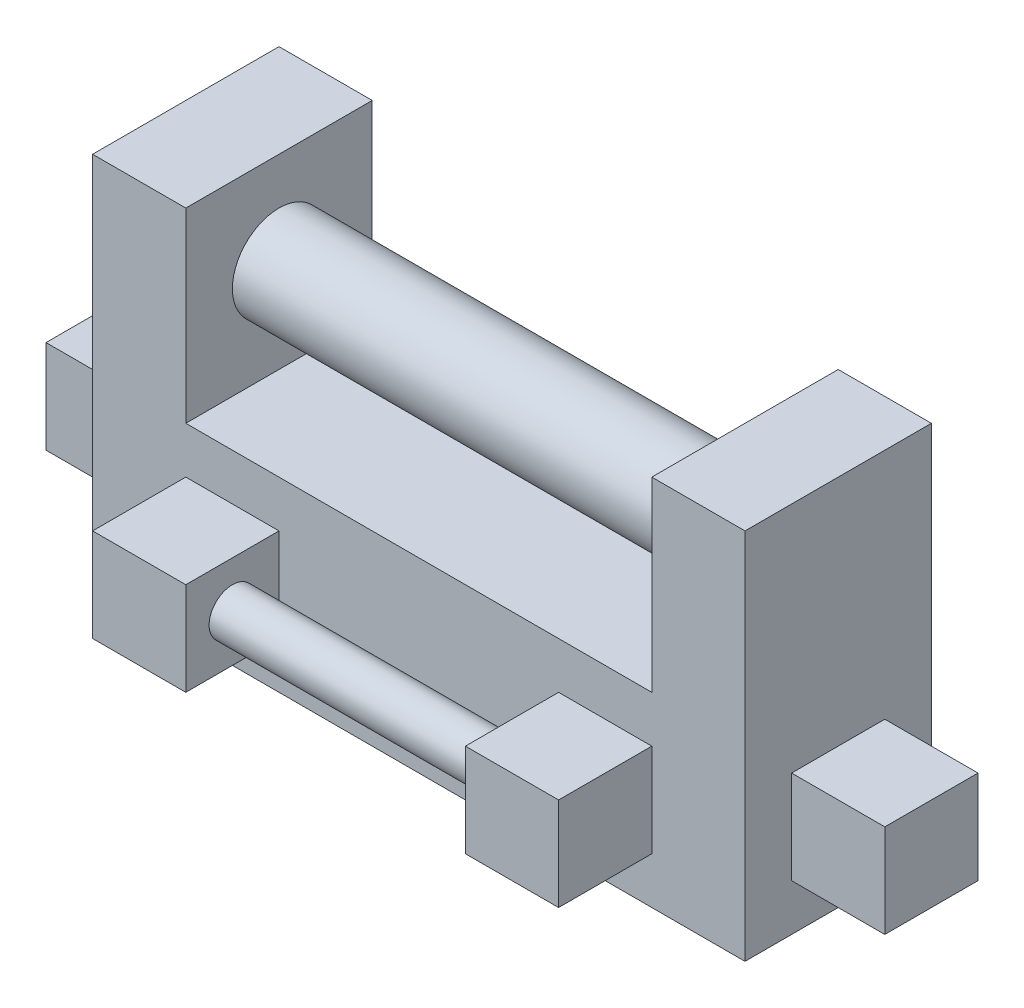
SolidWorks part; units mm, degrees
ref_plane "Front Plane" through (0, 0, 0) normal (0, 0, 1) x (1, 0, 0)
ref_plane "Top Plane" through (0, 0, 0) normal (0, 1, 0) x (1, 0, 0)
ref_plane "Right Plane" through (0, 0, 0) normal (1, 0, 0) x (0, 0, -1)
sketch "Sketch1" plane through (0, 0, 0) normal (0, 0, 1) x (1, 0, 0)
  line L0 (0, 0) -> (0, 40)
  line L1 (0, 40) -> (10, 40)
  line L2 (10, 40) -> (10, 20)
  line L3 (10, 20) -> (60, 20)
  line L4 (60, 20) -> (60, 40)
  line L5 (60, 40) -> (70, 40)
  line L6 (70, 40) -> (70, 0)
  line L7 (70, 0) -> (0, 0)
  line L9 (0, 5) -> (-10, 5)
  line L10 (0, 5) -> (0, 15)
  line L11 (0, 15) -> (-10, 15)
  line L12 (-10, 5) -> (-10, 15)
  line L13 (70, 5) -> (80, 5)
  line L14 (70, 5) -> (70, 15)
  line L15 (70, 15) -> (80, 15)
  line L16 (80, 5) -> (80, 15)
  line L17 (10, 5) -> (20, 5)
  line L18 (10, 5) -> (10, 15)
  line L19 (10, 15) -> (20, 15)
  line L20 (20, 5) -> (20, 15)
  line L21 (50, 5) -> (60, 5)
  line L22 (50, 5) -> (50, 15)
  line L23 (50, 15) -> (60, 15)
  line L24 (60, 5) -> (60, 15)
  point P25 (15, 5)
  dimension "D1" = 40
  dimension "D2" = 70
  dimension "D3" = 10
  dimension "D4" = 10
  dimension "D5" = 90
  dimension "D6" = 10
  dimension "D7" = 50
  dimension "D8" = 10
  dimension "D9" = 10
  dimension "D10" = 10
  dimension "D11" = 10
  dimension "D12" = 25
  dimension "D13" = 5
  dimension "D14" = 25
  dimension "D15" = 5
  dimension "D16" = 5
  dimension "D17" = 10
  dimension "D18" = 10
  dimension "D19" = 10
extrude "Boss-Extrude1" add sketch "Sketch1" along normal mid plane 20 contours L7 L6 L5 L4 L3 L2 L1 L0 L24 L21 L22 L23 L20 L17 L18 L19 region at (35, 15, 0)
extrude "Boss-Extrude2" add sketch "Sketch1<3>" along normal mid plane 10 contours L13 L16 L15 L6 | L12 L9 L0 L11 region at (-5, 10, 0) region at (75, 10, 0)
sketch "Sketch1<3>" plane through (0, 0, 0) normal (0, 0, 1) x (1, 0, 0) same geometry as "Sketch1"
extrude "Boss-Extrude3" add sketch "Sketch1<4>" along normal mid plane 40 contours L17 L20 L19 L18 | L21 L24 L23 L22 region at (15, 10, 0) region at (55, 10, 0)
sketch "Sketch1<4>" plane through (0, 0, 0) normal (0, 0, 1) x (1, 0, 0) same geometry as "Sketch1"
sketch "Sketch2" plane through (10, 0, 0) normal (1, 0, 0) x (0, 0, -1)
  line L0 (-10, 40) -> (-10, 0) construction
  line L1 (-10, 40) -> (10, 40) construction
  circle A0 centre (0, 30) radius 5
  dimension "D1" = 10
  dimension "D2" = 10
  dimension "D3" = 10
extrude "Boss-Extrude4" add sketch "Sketch2" along normal up to next
sketch "Sketch3" plane through (20, 0, 0) normal (1, 0, 0) x (0, 0, -1)
  line L1 (-20, 15) -> (-10, 15) construction
  line L2 (-20, 5) -> (-20, 15) construction
  circle A0 centre (-15, 10) radius 2.5
  dimension "D1" = 5
  dimension "D2" = 5
  dimension "D3" = 5
extrude "Boss-Extrude5" add sketch "Sketch3" along normal up to next
mirror "Mirror1" about plane through (0, 0, 0) normal (0, 0, 1) of "Boss-Extrude5"
